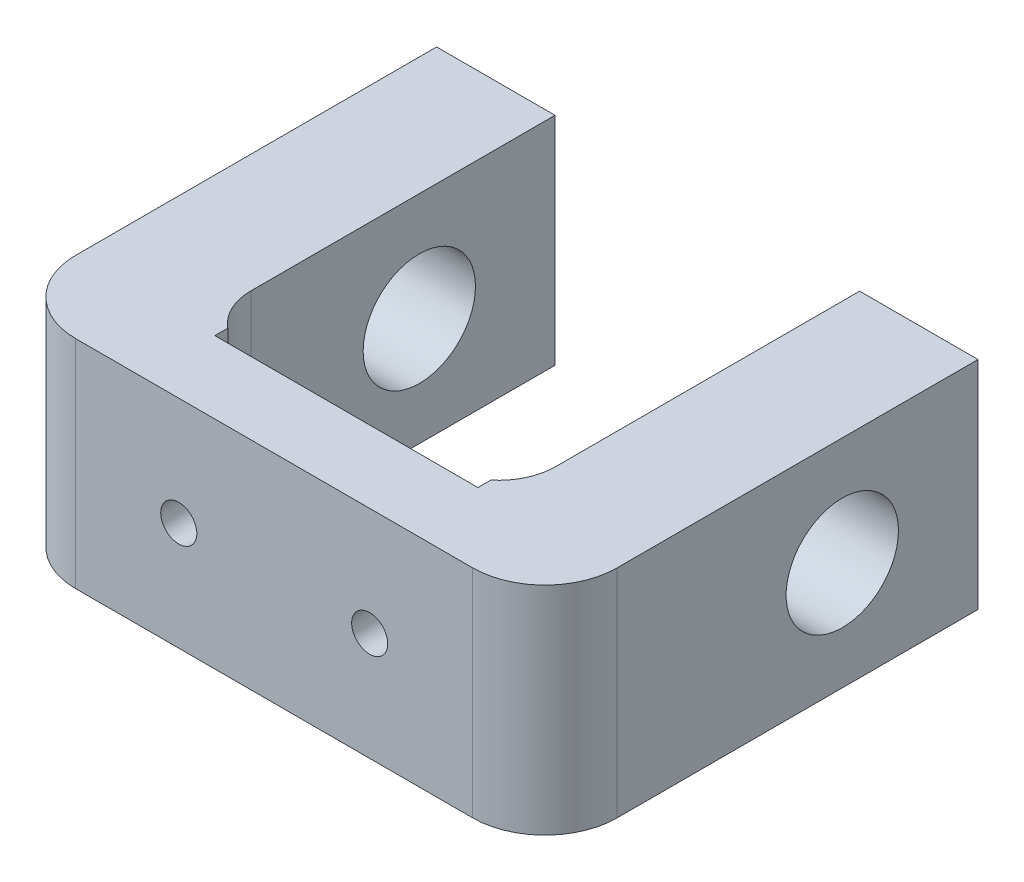
SolidWorks part; units mm, degrees
ref_plane "Front Plane" through (0, 0, 0) normal (0, 0, 1) x (1, 0, 0)
ref_plane "Top Plane" through (0, 0, 0) normal (0, 1, 0) x (1, 0, 0)
ref_plane "Right Plane" through (0, 0, 0) normal (1, 0, 0) x (0, 0, -1)
sketch "Sketch1" plane through (0, 0, 0) normal (0, 1, 0) x (1, 0, 0)
  line L0 (-47.625, 76.2) -> (-47.625, 12.7)
  line L1 (-34.925, 0) -> (34.925, 0)
  line L2 (47.625, 12.7) -> (47.625, 76.2)
  line L3 (47.625, 76.2) -> (26.797, 76.2)
  line L4 (26.797, 76.2) -> (26.797, 22.7)
  line L5 (-47.625, 76.2) -> (-26.797, 76.2)
  line L6 (-26.797, 76.2) -> (-26.797, 22.7)
  line L7 (-16.797, 12.7) -> (16.797, 12.7)
  arc A2 (-16.797, 12.7) -> (-26.797, 22.7) centre (-16.797, 22.7) cw
  arc A3 (16.797, 12.7) -> (26.797, 22.7) centre (16.797, 22.7) ccw
  arc A4 (-34.925, 0) -> (-47.625, 12.7) centre (-34.925, 12.7) cw
  arc A5 (34.925, 0) -> (47.625, 12.7) centre (34.925, 12.7) ccw
  point P2 (0, 0)
  point P23 (0, 0)
  dimension "D1" = 10
  dimension "D2" = 10
  dimension "D7" = 12.7
  dimension "D6" = 12.7
  dimension "D3" = 20.828
  dimension "D4" = 12.7
  dimension "D5" = 95.25
  dimension "D8" = 76.2
extrude "Boss-Extrude1" add sketch "Sketch1" along normal blind 38.1
sketch "Sketch2" plane through (47.625, 0, 0) normal (1, 0, 0) x (0, 0, -1)
  line L0 (76.2, 19.05) -> (12.7, 19.05) construction
  line L1 (76.2, 38.1) -> (76.2, 0) construction
  line L2 (12.7, 38.1) -> (12.7, 0) construction
  line L3 (0, 38.1) -> (0, 0) construction
  circle A0 centre (52.324, 19.05) radius 9.8806
  dimension "D1" = 19.7612
  dimension "D2" = 52.324
extrude "Cut-Extrude1" cut sketch "Sketch2" against normal through all
sketch "Sketch3" plane through (0, 0, -12.7) normal (0, 0, -1) x (-1, 0, 0)
  line L0 (-16.797, 38.1) -> (-16.797, 0) construction
  line L1 (16.797, 38.1) -> (16.797, 0) construction
  circle A0 centre (-16.797, 19.05) radius 3.175
  circle A1 centre (16.797, 19.05) radius 3.175
  dimension "D1" = 6.35
  dimension "D2" = 6.35
extrude "Cut-Extrude2" cut sketch "Sketch3" against normal through all and the other way through all contours A0 | A1
ref_axis "Axis1" through (-19.972, 19.0487, -13.2174) along (0, -1, 0)
ref_axis "Axis2" through (19.972, 19.05, -13.2174) along (0, -1, 0)
sketch "Sketch4" plane through (0, 0, 0) normal (0, -1, 0) x (1, 0, 0)
  line L0 (16.797, -15.24) -> (16.797, -12.7) construction
  line L1 (23.147, -15.24) -> (-23.147, -15.24)
  line L2 (23.147, -15.24) -> (23.147, -12.7)
  line L3 (23.147, -12.7) -> (-23.147, -12.7)
  line L4 (-23.147, -15.24) -> (-23.147, -12.7)
  line L5 (-16.797, -15.24) -> (-16.797, -12.7) construction
  dimension "D1" = 6.35
  dimension "D2" = 6.35
  dimension "D3" = 2.54
extrude "Cut-Extrude3" cut sketch "Sketch4" against normal through all
